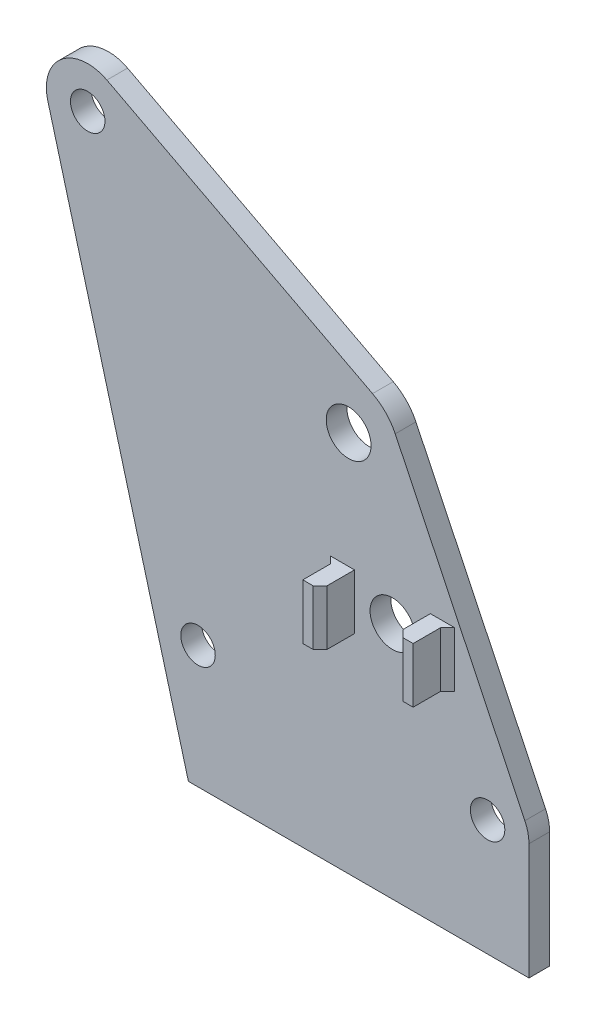
SolidWorks part; units mm, degrees
ref_plane "Front Plane" through (0, 0, 0) normal (0, 0, 1) x (1, 0, 0)
ref_plane "Top Plane" through (0, 0, 0) normal (0, 1, 0) x (1, 0, 0)
ref_plane "Right Plane" through (0, 0, 0) normal (1, 0, 0) x (0, 0, -1)
sketch "Sketch1" plane through (0, 0, 0) normal (0, 0, 1) x (1, 0, 0)
  line L0 (-174.1487, -16.8684) -> (5.8513, -16.8684) construction
  line L5 (-174.1487, -16.8684) -> (5.8513, -16.8684) construction
  line L6 (-58, 60) -> (-42, 0.929) construction
  line L7 (-42, 0.929) -> (0, 0) construction
  line L8 (0, 0) -> (-13.7985, 17.748) construction
  line L9 (-13.7985, 17.748) -> (-20.1576, 38.5476) construction
  line L10 (-20.1576, 38.5476) -> (-58, 60) construction
  line L11 (-58, 60) -> (0, 0) construction
  line L12 (-63.7913, 58.4314) -> (-43.3956, -16.8684)
  line L13 (-55.2228, 65.3186) -> (-16.6861, 45.1959)
  line L14 (-13.3956, 41.7918) -> (5.4096, 2.5954)
  line L15 (6, 0) -> (6, -16.8684)
  line L16 (-43.3956, -16.8684) -> (6, -16.8684)
  circle A0 centre (0, 0) radius 2.5
  circle A1 centre (-58, 60) radius 2.5
  circle A2 centre (-42, 0.929) radius 2.5 construction
  circle A3 centre (-42, 0.929) radius 2.5
  circle A4 centre (-13.7985, 17.748) radius 3.8 construction
  circle A5 centre (-13.7985, 17.748) radius 3.8 construction
  circle A6 centre (-20.1576, 38.5476) radius 10 construction
  circle A7 centre (-20.1576, 38.5476) radius 10 construction
  circle A8 centre (-20.1576, 38.5476) radius 3.25
  circle A9 centre (-42, 0.929) radius 6 construction
  circle A10 centre (-58, 60) radius 6 construction
  circle A11 centre (-20.1576, 38.5476) radius 7.5 construction
  circle A12 centre (0, 0) radius 6 construction
  arc A13 (-63.7913, 58.4314) -> (-55.2228, 65.3186) centre (-58, 60) cw
  arc A14 (-16.6861, 45.1959) -> (-13.3956, 41.7918) centre (-20.1576, 38.5476) cw
  arc A15 (5.4096, 2.5954) -> (6, 0) centre (0, 0) cw
  circle A16 centre (-13.7985, 17.748) radius 3.25
  dimension "D1" = 5
  dimension "D4" = 6.5
  dimension "D5" = 12
  dimension "D6" = 15
  dimension "D7" = 6.5
  dimension "D2" = 58
  dimension "D3" = 60
extrude "Boss-Extrude1" add sketch "Sketch1" along normal blind 3
sketch "Sketch2" plane through (0, 0, 3) normal (0, 0, 1) x (1, 0, 0)
  line L0 (-8.2985, 21.748) -> (-5.7985, 21.748)
  line L1 (-19.2985, 21.748) -> (-8.2985, 21.748) construction
  line L2 (-19.2985, 21.748) -> (-19.2985, 13.748)
  line L3 (-19.2985, 13.748) -> (-8.2985, 13.748) construction
  line L4 (-8.2985, 21.748) -> (-8.2985, 13.748)
  line L5 (-13.7985, 13.748) -> (-13.7985, 21.748) construction
  line L6 (-19.2985, 17.748) -> (-8.2985, 17.748) construction
  line L7 (-5.7985, 21.748) -> (-5.7985, 13.748)
  line L8 (-5.7985, 13.748) -> (-8.2985, 13.748)
  line L9 (-19.2985, 13.748) -> (-21.7985, 13.748)
  line L10 (-21.7985, 13.748) -> (-21.7985, 21.748)
  line L11 (-21.7985, 21.748) -> (-19.2985, 21.748)
  point P0 (-13.7985, 17.748)
  dimension "D1" = 11
  dimension "D2" = 2.5
  dimension "D3" = 8
extrude "Boss-Extrude2" add sketch "Sketch2" along normal blind 5
chamfer "Chamfer1" distance 1 angle 45 4 edges at (-19.2985, 17.748, 8) (-8.2985, 17.748, 8) (-21.7985, 17.748, 3) (-5.7985, 17.748, 3)
